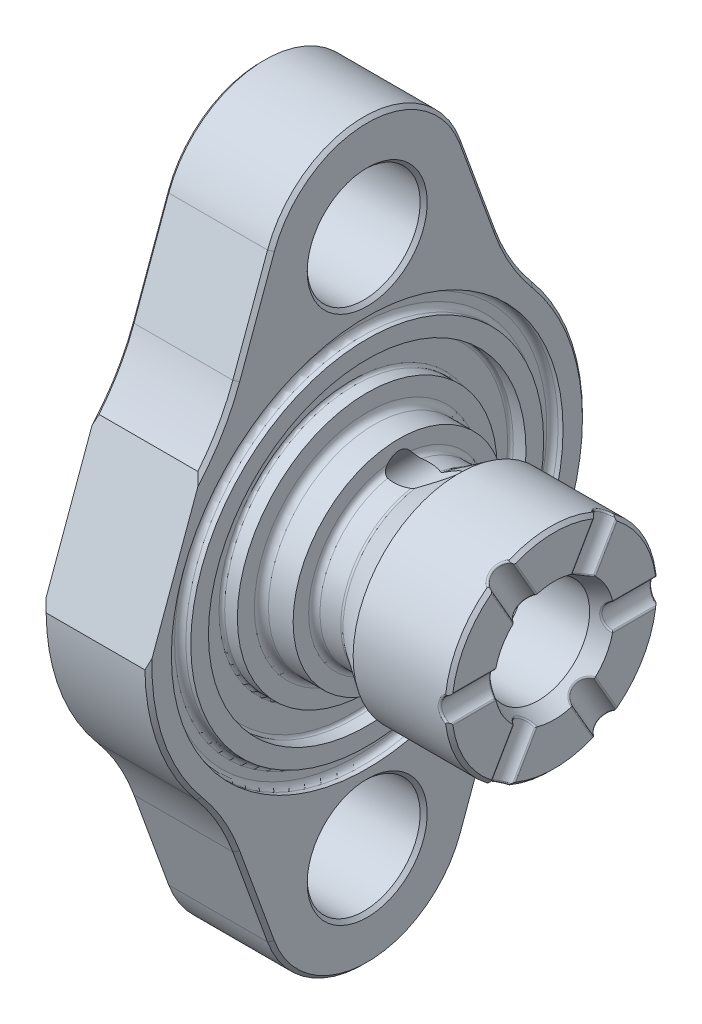
SolidWorks part; units mm, degrees
material "17CrNiMo6"
ref_plane "Front Plane" through (0, 0, 0) normal (0, 0, 1) x (1, 0, 0)
ref_plane "Top Plane" through (0, 0, 0) normal (0, 1, 0) x (1, 0, 0)
ref_plane "Right Plane" through (0, 0, 0) normal (1, 0, 0) x (0, 0, -1)
sketch "Sketch1" plane through (0, 0, 0) normal (0, 0, 1) x (1, 0, 0)
  line L0 (0, 0) -> (0, 52.5)
  line L1 (0, 52.5) -> (15, 52.5)
  line L2 (15, 52.5) -> (15, 27.75)
  line L3 (15, 27.75) -> (14.3, 27.75)
  line L4 (13.5, 26.95) -> (13.5, 25.8)
  line L5 (14.3, 25) -> (15, 25)
  line L6 (15, 25) -> (15, 22.5)
  line L7 (15, 22.5) -> (13.2, 22.5)
  line L8 (12.8, 22.1) -> (12.8, 18.8)
  line L9 (13.2, 18.4) -> (15, 18.4)
  line L10 (15, 18.4) -> (15, 15.9975)
  line L11 (16, 14.9975) -> (19.5, 14.9975)
  line L12 (19.5, 14.9975) -> (19.5, 12.8)
  line L13 (20.3, 12) -> (23.2579, 12)
  line L14 (23.7015, 12.1342) -> (28, 14.9975)
  line L15 (28, 14.9975) -> (41.5, 14.9975)
  line L16 (41.5, 14.9975) -> (41.5, 8.5)
  line L17 (41.5, 8.5) -> (39.25, 7.265)
  line L18 (39.25, 7.265) -> (30, 7.265)
  line L19 (30, 7.265) -> (30, 7.5)
  line L20 (30, 7.5) -> (28.5, 7.5)
  line L21 (28.5, 7.5) -> (27.9082, 6.515)
  line L22 (27.9082, 6.515) -> (13.5, 6.515)
  line L23 (13.5, 6.515) -> (13.5, 6.9)
  line L24 (11.5, 6.9) -> (7.3541, 0)
  line L25 (0, 0) -> (64.1591, 0) construction
  line L26 (13.5, 6.9) -> (11.5, 6.9)
  line L27 (0, 0) -> (7.3541, 0)
  arc A0 (13.5, 26.95) -> (14.3, 27.75) centre (14.3, 26.95) cw
  arc A1 (14.3, 25) -> (13.5, 25.8) centre (14.3, 25.8) cw
  arc A2 (13.2, 22.5) -> (12.8, 22.1) centre (13.2, 22.1) ccw
  arc A3 (13.2, 18.4) -> (12.8, 18.8) centre (13.2, 18.8) cw
  arc A4 (20.3, 12) -> (19.5, 12.8) centre (20.3, 12.8) cw
  arc A5 (23.7015, 12.1342) -> (23.2579, 12) centre (23.2579, 12.8) cw
  arc A6 (16, 14.9975) -> (15, 15.9975) centre (16, 15.9975) cw
  point P25 (21.5, 12)
  point P42 (23.5, 12)
  dimension "D29" = 0.8
  dimension "D30" = 1
  dimension "D31" = 0.4
  dimension "D32" = 0.8
  dimension "D1" = 59
  dimension "D2" = 15
  dimension "D3" = 105
  dimension "D4" = 11.5
  dimension "D5" = 14.53
  dimension "D6" = 13.8
  dimension "D7" = 15
  dimension "D8" = 29.995
  dimension "D9" = 24
  dimension "D10" = 26.5
  dimension "D11" = 13
  dimension "D12" = 59
  dimension "D13" = 2.25
  dimension "D14" = 17
  dimension "D15" = 13.03
  dimension "D16" = 30
  dimension "D17" = 22
  dimension "D18" = 13.5
  dimension "D19" = 18
  dimension "D20" = 36.8
  dimension "D21" = 45
  dimension "D22" = 50
  dimension "D23" = 55.5
  dimension "D24" = 1.5
  dimension "D25" = 2.2
  dimension "D26" = 2
  dimension "D27" = 41.5
  dimension "D28" = 28
revolve "Revolve1" add sketch "Sketch1" angle 360 about L25
sketch "Sketch2" plane through (0, 0, 0) normal (-1, 0, 0) x (0, 0, 1)
  line L0 (0, 0) -> (70.5057, 0) construction
  line L1 (0, 0) -> (0, 55.746) construction
  line L2 (13.6255, 42.4593) -> (18.5464, 28.9393)
  line L3 (-13.6255, 42.4593) -> (-18.5464, 28.9393)
  line L4 (13.6255, -42.4593) -> (18.5464, -28.9393)
  line L5 (-13.6255, -42.4593) -> (-18.5464, -28.9393)
  arc A0 (13.6255, 42.4593) -> (-13.6255, 42.4593) centre (0, 37.5) ccw
  arc A1 (23.7517, -19.9213) -> (23.7517, 19.9213) centre (0, 0) ccw
  arc A2 (23.7517, 19.9213) -> (18.5464, 28.9393) centre (46.7372, 39.1999) cw
  arc A3 (-23.7517, 19.9213) -> (-18.5464, 28.9393) centre (-46.7372, 39.1999) ccw
  arc A4 (-23.7517, -19.9213) -> (-23.7517, 19.9213) centre (0, 0) cw
  arc A5 (23.7517, -19.9213) -> (18.5464, -28.9393) centre (46.7372, -39.1999) ccw
  arc A6 (13.6255, -42.4593) -> (-13.6255, -42.4593) centre (0, -37.5) cw
  arc A7 (-23.7517, -19.9213) -> (-18.5464, -28.9393) centre (-46.7372, -39.1999) cw
  circle A8 centre (0, 37.5) radius 8 construction
  circle A9 centre (0, -37.5) radius 8 construction
  dimension "D1" = 29
  dimension "D2" = 62
  dimension "D3" = 75
  dimension "D5" = 30
  dimension "D6" = 104
  dimension "D7" = 16
  dimension "D8" = 91
  dimension "D4" = 20
extrude "Cut-Extrude1" cut sketch "Sketch2" against normal through all flip side to cut
sketch "Sketch3" plane through (0, 0, 0) normal (-1, 0, 0) x (0, 0, 1)
  circle A0 centre (0, 37.5) radius 8
  dimension "D1" = 16
extrude "Cut-Extrude2" cut sketch "Sketch3" against normal through all
mirror "Mirror1" about plane through (0, 0, 0) normal (0, 1, 0) of "Cut-Extrude2"
hole_wizard "Hole1" [suppressed] positions "Sketch7" profile "Sketch6" legacy
sketch "Sketch7" plane through (0, 0, 0) normal (-1, 0, 0) x (0, 0, 1)
  point P0 (0, 0)
sketch "Sketch6" plane through (0, 0, 0) normal (0, 1, 0) x (0, 0, 1)
  line L0 (0, 0) -> (0, 6.2017)
  line L1 (0, 6.2017) -> (2, 5)
  line L2 (2, 5) -> (2, 1.7321)
  line L3 (2, 1.7321) -> (3, 0)
  line L4 (3, 0) -> (0, 0)
  line L5 (0, -14.3089) -> (0, 102.4216) construction
  line L6 (0, 6.2017) -> (-2, 5) construction
  line L7 (-2, 1.7321) -> (-3, 0) construction
  dimension "Diameter" = 4
  dimension "Depth" = 5
  dimension "C-Sink Diameter" = 6
  dimension "C-Sink Angle" = 60
  dimension "Drill Angle" = 118
chamfer "Chamfer2" distance 0.5 angle 45 1 edges at (41.5, 0, 14.9975)
sketch "Sketch8" plane through (0, 0, 0) normal (0, 0, 1) x (1, 0, 0)
  line L0 (0, 0) -> (52.9452, 0) construction
  line L1 (41.5, -14.9975) -> (41.5, 14.9975) construction
  line L2 (45.4183, -2) -> (40.3, -2) construction
  line L3 (45.4183, -2) -> (45.4183, 2) construction
  line L4 (45.4183, 2) -> (40.3, 2) construction
  line L5 (40.3, -2) -> (40.3, 2) construction
  line L7 (41.5, 1.833) -> (44.8657, 1.833)
  line L8 (44.8657, 1.833) -> (44.8657, -1.833)
  line L9 (41.5, -1.833) -> (44.8657, -1.833)
  line L10 (41.5, -14.4975) -> (41.5, 14.4975) construction
  arc A0 (41.5, 1.833) -> (41.5, -1.833) centre (42.3, 0) ccw
  dimension "D4" = 2
  dimension "D5" = 1.2
  dimension "D1" = 4
  dimension "D2" = 2
  dimension "D3" = 1.2
  dimension "D7" = 3.3657
extrude "Cut-Extrude4" cut sketch "Sketch8" against normal through all
ref_axis "Axis1" through (30, 0, 0) along (1, 0, 0)
pattern_circular "CirPattern1" count 6 over 360 about axis through (30, 0, 0) along (1, 0, 0) of "Cut-Extrude4"
sketch "Sketch9" plane through (0, 0, 0) normal (-1, 0, 0) x (0, 0, 1)
  line L0 (12.5843, 50.2154) -> (38.1523, -20.0324)
  line L1 (38.1523, -20.0324) -> (42.1987, -18.5596)
  line L2 (42.1987, -18.5596) -> (16.6306, 51.6881)
  line L3 (16.6306, 51.6881) -> (12.5843, 50.2154)
  line L4 (0, 0) -> (50.117, 0) construction
  dimension "D1" = 70
  dimension "D2" = 29
extrude "Cut-Extrude5" cut sketch "Sketch9" against normal up to surface (15 mm away) up to face at (15, 37.5, 8)
ref_plane "Plane1" through (0, 0, 0) normal (0.7071, 0.7071, 0) x (0, 0, -1)
ref_plane "Plane2" through (16.75, 16.75, 0) normal (0.7071, 0.7071, 0) x (0, 0, -1)
sketch "Sketch10" plane through (16.75, 16.75, 0) normal (0.7071, 0.7071, 0) x (0, 0, -1)
  circle A0 centre (0, -6.7175) radius 2.5
  dimension "D1" = 5
extrude "Cut-Extrude6" cut sketch "Sketch10" against normal blind 12 and the other way through all
pattern_circular "CirPattern2" count 2 over 360 about axis through (30, 0, 0) along (1, 0, 0) of "Cut-Extrude6"
sketch "Sketch13" plane through (0, 0, 0) normal (-1, 0, 0) x (0, 0, 1)
  line L0 (0, 18.9466) -> (0, -21.9396) construction
  line L1 (4.9962, 8.7339) -> (4.9962, -7.6503) construction
  text T0 "3115 2077 03 - M\r\n11111 -  XX" font "Century Gothic" height 3.5
  point P5 (0, -21.9396)
  line B0 (4.9962, -4.4157) -> (4.9962, 0.1601)
  line B1 (5.9289, -3.7379) -> (5.9289, -0.3703)
  line B2 (5.1362, 0.0805) -> (5.7889, -0.2907)
  line B3 (9.8181, -1.6011) -> (9.8181, -0.803)
  line B4 (12.9876, 0.1601) -> (9.8181, -1.6011)
  line B5 (5.9289, -3.7379) -> (8.9351, -2.0797)
  line B6 (8.9351, -5.7609) -> (8.2121, -6.1792)
  line B7 (12.9876, -2.0855) -> (12.9876, 0.1601)
  line B8 (9.8181, -5.2793) -> (8.9351, -5.7609)
  line B9 (9.8181, -5.2793) -> (11.8573, -4.07)
  line B10 (4.9962, 0.1601) -> (4.9962, 3.6565)
  line B11 (8.453, 1.6908) -> (4.9962, 3.6565)
  line B12 (9.0756, -5.5569) -> (9.6781, -5.1996)
  line B13 (12.8476, -2.0855) -> (12.8476, -0.0779)
  line B14 (12.8476, -0.0779) -> (9.8181, -1.7612)
  line B15 (9.6781, -0.803) -> (9.6781, -5.1996)
  line B16 (8.3806, 1.5709) -> (5.1362, 3.4158)
  line B17 (5.1362, 0.2415) -> (5.1362, 3.4158)
  line B18 (9.0756, -1.9986) -> (9.0756, -5.5569)
  line B19 (5.1362, 0.2415) -> (9.0756, -1.9986)
  line B20 (8.9351, -5.5991) -> (8.1394, -6.0595)
  line B21 (5.1362, -4.4157) -> (5.1362, 0.0805)
  line B22 (9.8181, -1.7612) -> (9.8181, -5.1166)
  line B23 (9.8181, -5.1166) -> (11.7859, -3.9496)
  line B24 (5.7889, -3.9751) -> (5.7889, -0.2907)
  line B25 (5.7889, -3.9751) -> (8.9351, -2.2396)
  line B26 (8.9351, -2.2396) -> (8.9351, -5.5991)
  line B27 (5.9289, -0.3703) -> (8.9351, -2.0797)
  arc B28 (11.8573, -4.07) -> (12.9876, -2.0855) centre (10.6804, -2.0855) ccw
  arc B29 (4.9962, -4.4157) -> (8.2121, -6.1792) centre (7.0876, -4.4157) ccw
  arc B30 (9.8181, -0.803) -> (8.453, 1.6908) centre (6.8575, -0.803) ccw
  arc B31 (11.7859, -3.9496) -> (12.8476, -2.0855) centre (10.6804, -2.0855) ccw
  arc B32 (9.6781, -0.803) -> (8.3806, 1.5709) centre (6.8575, -0.803) ccw
  arc B33 (5.1362, -4.4157) -> (8.1394, -6.0595) centre (7.0876, -4.4157) ccw
sketch_block_instance "SKETCH LOGO-1"
sketch_block "SKETCH LOGO" parameters "D1"=29.059, "D2"=11.4163, "D3"=29.624, "D4"=6.8884
extrude "Extrude1" cut sketch "Sketch13" against normal blind 0.1
chamfer "Chamfer3" distance 0.5 angle 45 28 edges at (15, -10.7756, 29.0669) (15, -24.2028, 20.7548) (15, -35.6993, 16.086) (15, -52, 0) (15, -35.6993, -16.086) (15, -24.2028, -20.7548) (15, 0, -31) (15, 24.3744, 20.6565) (15, 24.2028, -20.7548) (15, 35.6993, 16.086) (15, 35.6993, -16.086) (15, 52, 0) (15, 37.5, 8) (15, -37.5, 8) (0, -37.5, 8) (0, 37.5, 8) (0, -10.7756, 29.0669) (0, 24.3744, 20.6565) (0, -24.2028, 20.7548) (0, 35.6993, 16.086) (0, -35.6993, 16.086) (0, 52, 0) (0, -52, 0) (0, 35.6993, -16.086) (0, -35.6993, -16.086) (0, 24.2028, -20.7548) (0, -24.2028, -20.7548) (0, 0, -31)
fillet "Fillet1" radius 0.25 36 edges at (41.5, -1.833, -11.3406) (40.3114, 0.2136, -7.8447) (40.322, -0.2958, -14.9946) (41.5, 1.833, -11.3406) (41.5, -10.7377, -4.0828) (40.3114, -6.6869, -4.1074) (40.3, -12.985, -7.5043) (40.3114, 6.9005, -3.7373) (40.3504, 13.2055, -7.1091) (41.5, -8.9047, 7.2577) (40.3114, -6.9005, 3.7373) (40.3, -12.9914, 7.4932) (41.5, 1.833, 11.3406) (40.3114, -0.2136, 7.8447) (40.313, -0.2274, 14.9958) (41.5, 10.7377, 4.0828) (40.3114, 6.6869, 4.1074) (40.3, 12.985, 7.5043) (41.5, -8.9047, -7.2577) (41.5, 8.9047, -7.2577) (41.5, -10.7377, 4.0828) (41.5, -1.833, 11.3406) (41.5, 8.9047, 7.2577) (41.5, 10.7377, -4.0828)
